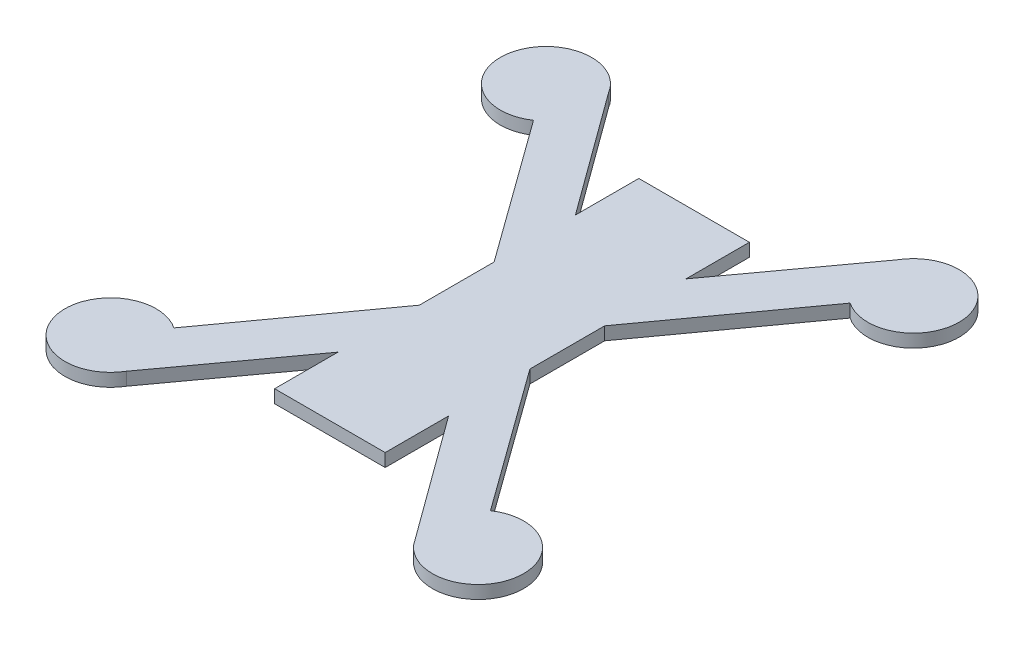
SolidWorks part; units mm, degrees
ref_plane "Front Plane" through (0, 0, 0) normal (0, 0, 1) x (1, 0, 0)
ref_plane "Top Plane" through (0, 0, 0) normal (0, 1, 0) x (1, 0, 0)
ref_plane "Right Plane" through (0, 0, 0) normal (1, 0, 0) x (0, 0, -1)
sketch "Frame Sketch" plane through (0, 0, 0) normal (0, 1, 0) x (1, 0, 0)
  line L0 (0, 0) -> (0, 124.363) construction
  line L5 (-17, 11.5) -> (-48.6747, 55.2899)
  line L6 (-48.6747, 0) -> (67.0859, 0) construction
  line L11 (0, 0) -> (0, -108.0455) construction
  line L22 (-17, 36.5) -> (-46.0248, 76.2899)
  line L23 (-17, 56) -> (17, 56)
  line L24 (-17, 56) -> (-17, -56)
  line L25 (-17, -56) -> (17, -56)
  line L26 (17, 56) -> (17, -56)
  line L27 (-17, 56) -> (17, -56) construction
  line L28 (-17, -56) -> (17, 56) construction
  line L29 (-17, -11.5) -> (-48.6747, -55.2899)
  line L30 (-17, -36.5) -> (-17, -11.5)
  line L31 (-17, -36.5) -> (-46.0248, -76.2899)
  line L32 (-48.6747, -55.2899) -> (-46.0248, -76.2899)
  line L33 (17, -36.5) -> (17, -11.5)
  line L34 (17, -36.5) -> (46.0248, -76.2899)
  line L35 (-17, 36.5) -> (-17, 11.5)
  line L36 (-48.6747, 55.2899) -> (-46.0248, 76.2899)
  line L37 (48.6747, -55.2899) -> (46.0248, -76.2899)
  line L38 (17, -11.5) -> (48.6747, -55.2899)
  line L39 (17, 11.5) -> (48.6747, 55.2899)
  line L40 (17, 36.5) -> (17, 11.5)
  line L41 (17, 36.5) -> (46.0248, 76.2899)
  line L42 (48.6747, 55.2899) -> (46.0248, 76.2899)
  circle A0 centre (-56.5031, 66.9449) radius 14.04
  circle A5 centre (-56.5031, -66.9449) radius 14.04
  circle A6 centre (56.5031, -66.9449) radius 14.04
  circle A7 centre (56.5031, 66.9449) radius 14.04
  point P0 (0, 0)
  point P6 (0, 0)
  point P36 (0, 0)
  dimension "D1" = 25
  dimension "D2" = 21
  dimension "D3" = 112
  dimension "D4" = 34
extrude "Boss-Extrude4" add sketch "Frame Sketch" along normal blind 4 contours L26 L23 L24 L25 | L37 A6 | L34 L37 L38 L33 | L39 L42 L41 L40 | A7 | L22 L36 L5 L35 | A0 | L29 L32 L31 L30 | A5 region at (0, 0, 0) region at (57.9322, 0, 67.1253)
